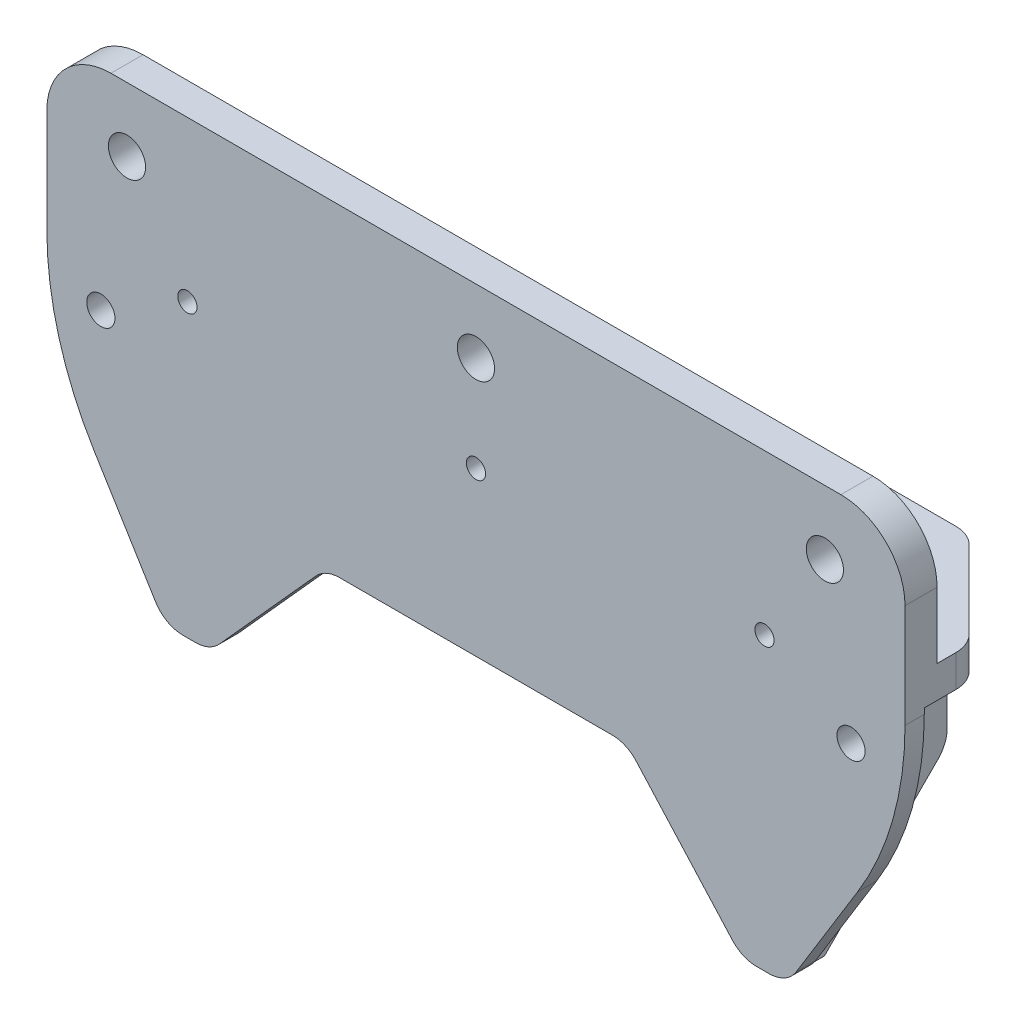
SolidWorks part; units mm, degrees
note: The reader was unsure of these and kept them because the rebuilt part matched: shared geometry of "Szkic1<3>".
material "ABS"
ref_plane "Płaszczyzna przednia" through (0, 0, 0) normal (0, 0, 1) x (1, 0, 0)
ref_plane "Płaszczyzna górna" through (0, 0, 0) normal (0, 1, 0) x (1, 0, 0)
ref_plane "Płaszczyzna prawa" through (0, 0, 0) normal (1, 0, 0) x (0, 0, -1)
sketch "Szkic1" plane through (0, 0, 0) normal (0, 0, 1) x (1, 0, 0)
  line L0 (-56.033, 5.445) -> (60.967, 5.445) construction
  line L1 (2.467, 5.445) -> (2.467, 17.945) construction
  line L2 (2.467, 17.945) -> (-81.033, 17.945) construction
  line L3 (2.467, 17.945) -> (113.467, 17.945) construction
  line L4 (113.467, 17.945) -> (113.467, -32.055) construction
  line L5 (113.467, -32.055) -> (-81.033, -32.055) construction
  line L6 (-81.033, -32.055) -> (-81.033, 17.945) construction
  line L7 (69.3854, 38.245) -> (69.3854, 17.945)
  line L8 (69.3854, -32.055) -> (-64.4514, -32.055)
  line L9 (69.3854, 38.245) -> (-64.4514, 38.245)
  line L10 (69.3854, 28.245) -> (2.467, 28.245) construction
  line L11 (-64.4514, 38.245) -> (-64.4514, 17.945)
  line L12 (69.3854, 17.945) -> (-64.4514, 17.945)
  line L13 (69.3854, -32.055) -> (69.3854, 17.945)
  line L14 (-64.4514, 17.945) -> (-64.4514, -32.055)
  line L15 (50.967, 17.945) -> (50.967, -32.055)
  line L16 (43.967, 17.945) -> (43.967, -32.055)
  line L17 (-46.033, 17.945) -> (-46.033, -32.055)
  line L18 (-39.033, 17.945) -> (-39.033, -32.055)
  line L19 (5.967, 17.945) -> (5.967, -32.055)
  line L20 (-1.033, 17.945) -> (-1.033, -32.055)
  line L21 (69.3854, 12.945) -> (-64.4514, 12.945)
  circle A0 centre (-56.033, 5.445) radius 2.2
  circle A1 centre (60.967, 5.445) radius 2.2
  circle A2 centre (56.8854, 28.245) radius 2.9
  circle A3 centre (2.467, 28.245) radius 2.9
  circle A4 centre (-51.9514, 28.245) radius 2.9
  point P24 (2.467, -32.055)
  point P25 (2.467, 38.245)
  dimension "D1" = 4.4
  dimension "D5" = 52.5
  dimension "D9" = 5.8
  dimension "D2" = 117
  dimension "D3" = 12.5
  dimension "D4" = 25
  dimension "D6" = 50
  dimension "D7" = 20.3
  dimension "D8" = 10
  dimension "D10" = 12.5
  dimension "D11" = 7
  dimension "D12" = 10
  dimension "D13" = 3.5
  dimension "D14" = 5
extrude "Dodanie-wyciągnięcie1" add sketch "Szkic1" along normal blind 5 contours L12 L7 L9 L11 A2 A3 A4 | L12 L14 L8 L13 A0 A1 | L12 L15 L8 L13 A1 | L12 L16 L8 L15 | L12 L19 L8 L16 | L20 L12 L18 L8 | L18 L12 L17 L8 | L17 L12 L14 L8 A0 | L21 L13 L12 L15 | L21 L15 L12 L16 | L21 L16 L12 L19 | L21 L19 L12 L20 | L21 L20 L12 L18 | L21 L18 L12 L17 | L21 L17 L12 L14
extrude "Dodanie-wyciągnięcie2" add sketch "Szkic1<3>" against normal blind 20 contours L21 L17 L12 L14 | L21 L18 L12 L17 | L21 L20 L12 L18 | L21 L19 L12 L20 | L21 L16 L12 L19 | L21 L15 L12 L16 | L21 L13 L12 L15 | L15 L21 L16 L8 | L19 L21 L20 L8 | L18 L21 L17 L8
sketch "Szkic1<3>" plane through (0, 0, 0) normal (0, 0, 1) x (1, 0, 0) same geometry as "Szkic1"
chamfer "Sfazowanie1" distance 20 angle 45 3 edges at (47.467, -32.055, -20) (2.467, -32.055, -20) (-42.533, -32.055, -20)
chamfer "Sfazowanie2" distance 15 angle 45 2 edges at (-64.4514, 15.445, -20) (69.3854, 15.445, -20)
sketch "Szkic3" plane through (0, 0, 0) normal (0, 0, -1) x (-1, 0, 0)
  line L0 (-60.967, 5.445) -> (-69.3854, 5.445) construction
  line L1 (-69.3854, 12.945) -> (-69.3854, -32.055) construction
  line L2 (-69.3854, 12.945) -> (-50.967, 12.945) construction
  line L3 (-69.3854, 12.945) -> (-50.967, 12.945) construction
  line L4 (-69.3854, -2.055) -> (-50.967, -2.055) construction
  line L5 (-69.3854, -2.055) -> (-50.967, -32.055)
  line L6 (-69.3854, -32.055) -> (-50.967, -32.055) construction
  line L7 (-50.967, -32.055) -> (-69.3854, -32.055)
  line L8 (-69.3854, -32.055) -> (-69.3854, -2.055)
  line L9 (-69.3854, 12.945) -> (64.4514, 12.945) construction
  line L10 (-2.467, 12.945) -> (-2.467, -32.055) construction
  line L11 (1.033, -32.055) -> (-5.967, -32.055) construction
  line L12 (64.4514, -32.055) -> (64.4514, -2.055)
  line L13 (46.033, -32.055) -> (64.4514, -32.055)
  line L14 (64.4514, -2.055) -> (46.033, -32.055)
extrude "Wytnij-wyciągnięcie1" cut sketch "Szkic3" against normal through all
sketch "Szkic4" plane through (0, 0, -20) normal (0, 0, -1) x (-1, 0, 0)
  line L0 (21.033, -12.055) -> (-25.967, -12.055)
  line L1 (-25.967, -12.055) -> (-43.967, -32.055)
  line L2 (39.033, -32.055) -> (-43.967, -32.055)
  line L3 (-2.467, -12.055) -> (-2.467, -32.055) construction
  line L4 (-5.967, -12.055) -> (-5.967, -32.055)
  line L5 (-5.967, -32.055) -> (1.033, -32.055)
  line L6 (1.033, -32.055) -> (1.033, -12.055)
  line L7 (1.033, -12.055) -> (-5.967, -12.055)
  line L8 (-5.967, -12.055) -> (-5.967, -32.055) construction
  line L9 (21.033, -12.055) -> (39.033, -32.055)
  line L10 (1.033, -32.055) -> (1.033, -12.055) construction
  line M19 (-5.967, -12.055) -> (1.033, -12.055)
  dimension "D1" = 0
extrude "Wytnij-wyciągnięcie2" cut sketch "Szkic4" against normal through all contours L2 L10 L0 L1 M19
chamfer "Sfazowanie3" distance 20 angle 45 1 edges at (2.467, -12.055, -20)
fillet "Zaokrąglenie1" radius 5 6 edges at (-46.033, 12.945, -10) (-39.033, 12.945, -10) (-1.033, 12.945, -10) (5.967, 12.945, -10) (43.967, 12.945, -10) (50.967, 12.945, -10)
fillet "Zaokrąglenie2" radius 5 11 edges at (-64.4514, 15.445, -5) (54.3854, 15.3167, -20) (-49.4514, 15.3167, -20) (69.3854, 15.445, -5) (50.967, -32.055, 2.5) (-46.033, -32.055, 2.5) (43.967, -32.055, 2.5) (-39.033, -32.055, 2.5) (-50.2319, 12.8804, -19.2196) (-42.533, -12.055, -20) (47.467, -12.055, -20)
fillet "Zaokrąglenie3" radius 10 2 edges at (-64.4514, 38.245, 2.5) (69.3854, 38.245, 2.5)
sketch "Szkic5" plane through (0, 0, -20) normal (0, 0, -1) x (-1, 0, 0)
  line L0 (-47.467, -9.9839) -> (-47.467, 17.945) construction
  line L1 (-50.967, -9.9839) -> (-43.967, -9.9839) construction
  line L2 (-52.3143, 17.945) -> (47.3804, 17.945) construction
  line L3 (-47.467, 17.945) -> (-2.467, 17.945) construction
  line L4 (-2.467, 17.945) -> (-2.467, 10.0161) construction
  circle A0 centre (-2.467, 13.3355) radius 1.5
  circle A1 centre (-47.467, 13.3355) radius 1.5
  circle A2 centre (42.533, 13.3355) radius 1.5
extrude "Wytnij-wyciągnięcie3" cut sketch "Szkic5" against normal through all
sketch "Szkic6" plane through (0, 0, -20) normal (0, 0, -1) x (-1, 0, 0)
  circle A0 centre (-47.467, 13.3355) radius 3.5
  circle A1 centre (-2.467, 13.3355) radius 3.5
  circle A2 centre (42.533, 13.3355) radius 3.5
extrude "Wytnij-wyciągnięcie4" cut sketch "Szkic6" against normal blind 5
fillet "Zaokrąglenie4" radius 2 1 edges at (2.467, 7.945, -20)
fillet "Zaokrąglenie5" radius 5 2 edges at (-21.033, -12.055, 2.5) (25.967, -12.055, 2.5)
fillet "Zaokrąglenie6" radius 50 2 edges at (69.3854, -2.055, 2.5) (-64.4514, -2.055, 2.5)
sketch "Szkic7" plane through (0, 12.945, 0) normal (0, -1, 0) x (1, 0, 0)
  line L0 (38.967, -10) -> (-34.033, -10) construction
  line L1 (38.967, -20) -> (38.967, 0) construction
  line L2 (-34.033, 0) -> (-34.033, -20) construction
  line L3 (24.967, -20) -> (24.967, 0) construction
  line L4 (38.967, -20) -> (10.967, -20) construction
  line L5 (38.967, 0) -> (10.967, 0) construction
  line L6 (-20.033, -20) -> (-20.033, 0) construction
  line L7 (-6.033, -20) -> (-34.033, -20) construction
  line L8 (-6.033, 0) -> (-34.033, 0) construction
  line L9 (38.967, -10.3) -> (-34.033, -10.3) construction
  circle A0 centre (24.967, -10.3) radius 2.8
  circle A1 centre (-20.033, -10.3) radius 2.8
  dimension "D2" = 5.6
  dimension "D3" = 5.6
  dimension "D1" = 0.3
extrude "Wytnij-wyciągnięcie5" cut sketch "Szkic7" against normal blind 4.6
chamfer "Sfazowanie4" distance 2 angle 45 16 edges at (-9.9196, -12.055, 0) (-46.8466, -30.5134, 0) (-30.033, -22.055, 0) (-38.2348, -31.036, 0) (34.967, -22.055, 0) (43.1687, -31.036, 0) (57.2131, -21.8812, 0) (51.7805, -30.5134, 0) (-64.4514, 12.507, 0) (69.3854, 12.507, 0) (14.8536, -12.055, 0) (-20.8404, -12.4875, 0) (25.7743, -12.4875, 0) (67.5025, -1.5231, 0) (-52.2792, -21.8812, 0) (-62.5686, -1.5231, 0)
